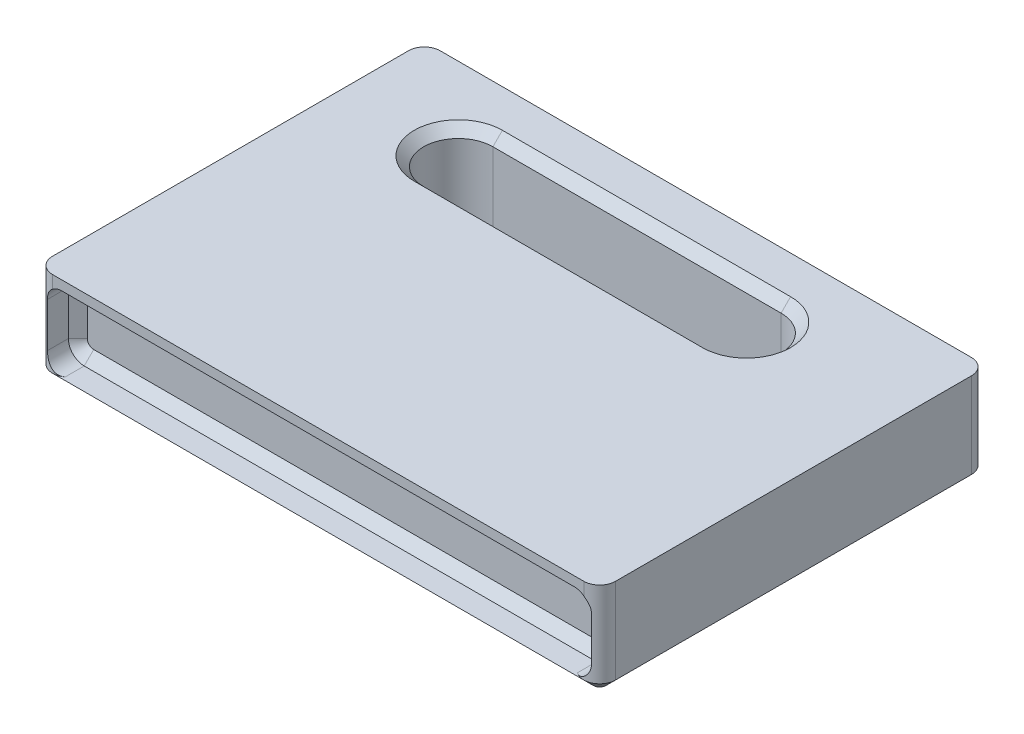
SolidWorks part; units mm, degrees
material "AISI 1020"
ref_plane "Front Plane" through (0, 0, 0) normal (0, 0, 1) x (1, 0, 0)
ref_plane "Top Plane" through (0, 0, 0) normal (0, 1, 0) x (1, 0, 0)
ref_plane "Right Plane" through (0, 0, 0) normal (1, 0, 0) x (0, 0, -1)
sketch "Sketch1" plane through (0, 0, 0) normal (0, 1, 0) x (1, 0, 0)
  line L1 (-88.8655, -61.1881) -> (88.8655, -61.1881)
  line L2 (-88.8655, -61.1881) -> (-88.8655, 61.1881)
  line L3 (-88.8655, 61.1881) -> (88.8655, 61.1881)
  line L4 (88.8655, -61.1881) -> (88.8655, 61.1881)
  line L5 (-88.8655, -61.1881) -> (88.8655, 61.1881) construction
  line L6 (-88.8655, 61.1881) -> (88.8655, -61.1881) construction
  point P0 (0, 0)
extrude "Boss-Extrude1" add sketch "Sketch1" along normal blind 30
sketch "Sketch2" plane through (0, 0, 61.1881) normal (0, 0, 1) x (1, 0, 0)
  line L8 (-85.8655, 3) -> (85.8655, 3)
  line L9 (85.8655, 3) -> (85.8655, 27)
  line L10 (85.8655, 27) -> (-85.8655, 27)
  line L11 (-85.8655, 27) -> (-85.8655, 3)
  line L12 (-85.8655, 3) -> (85.8655, 3)
  line L13 (85.8655, 3) -> (85.8655, 27)
  line L14 (85.8655, 27) -> (-85.8655, 27)
  line L15 (-85.8655, 27) -> (-85.8655, 3)
  dimension "D1" = 3
extrude "Cut-Extrude1" cut sketch "Sketch2" against normal blind 10
sketch "Sketch3" plane through (0, 30, 0) normal (0, 1, 0) x (1, 0, 0)
  line L0 (-52.2914, 35.3398) -> (38.6918, 35.3398) construction
  line L1 (-52.2914, 46.2578) -> (38.6918, 46.2578)
  line L2 (-52.2914, 24.4218) -> (38.6918, 24.4218)
  arc A0 (-52.2914, 46.2578) -> (-52.2914, 24.4218) centre (-52.2914, 35.3398) ccw
  arc A1 (38.6918, 24.4218) -> (38.6918, 46.2578) centre (38.6918, 35.3398) ccw
  point P2 (-6.7998, 35.3398)
extrude "Cut-Extrude2" cut sketch "Sketch3" against normal through all
fillet "Fillet1" radius 5 4 edges at (88.8655, 15, 61.1881) (-88.8655, 15, 61.1881) (88.8655, 15, -61.1881) (-88.8655, 15, -61.1881)
chamfer "Chamfer1" distance 3 angle 45 4 edges at (-63.2094, 30, -35.3398) (-6.7998, 30, -24.4218) (-6.7998, 30, -46.2578) (49.6098, 30, -35.3398)
chamfer "Chamfer2" distance 3 angle 45 12 edges at (87.401, 0, -59.7236) (0, 0, -61.1881) (-87.401, 0, -59.7236) (-88.8655, 0, 0) (-87.401, 0, 59.7236) (0, 0, 61.1881) (87.401, 0, 59.7236) (88.8655, 0, 0) (-6.7998, 0, -46.2578) (49.6098, 0, -35.3398) (-6.7998, 0, -24.4218) (-63.2094, 0, -35.3398)
fillet "Fillet2" radius 5 4 edges at (85.8655, 27, 55.9794) (85.8655, 3, 55.9794) (-85.8655, 3, 55.9794) (-85.8655, 27, 55.9794)
chamfer "Chamfer3" distance 3 angle 45 8 edges at (0, 27, 51.1881) (85.8655, 15, 51.1881) (0, 3, 51.1881) (-85.8655, 15, 51.1881) (84.401, 4.4645, 51.1881) (-84.401, 4.4645, 51.1881) (-84.401, 25.5355, 51.1881) (84.401, 25.5355, 51.1881)
